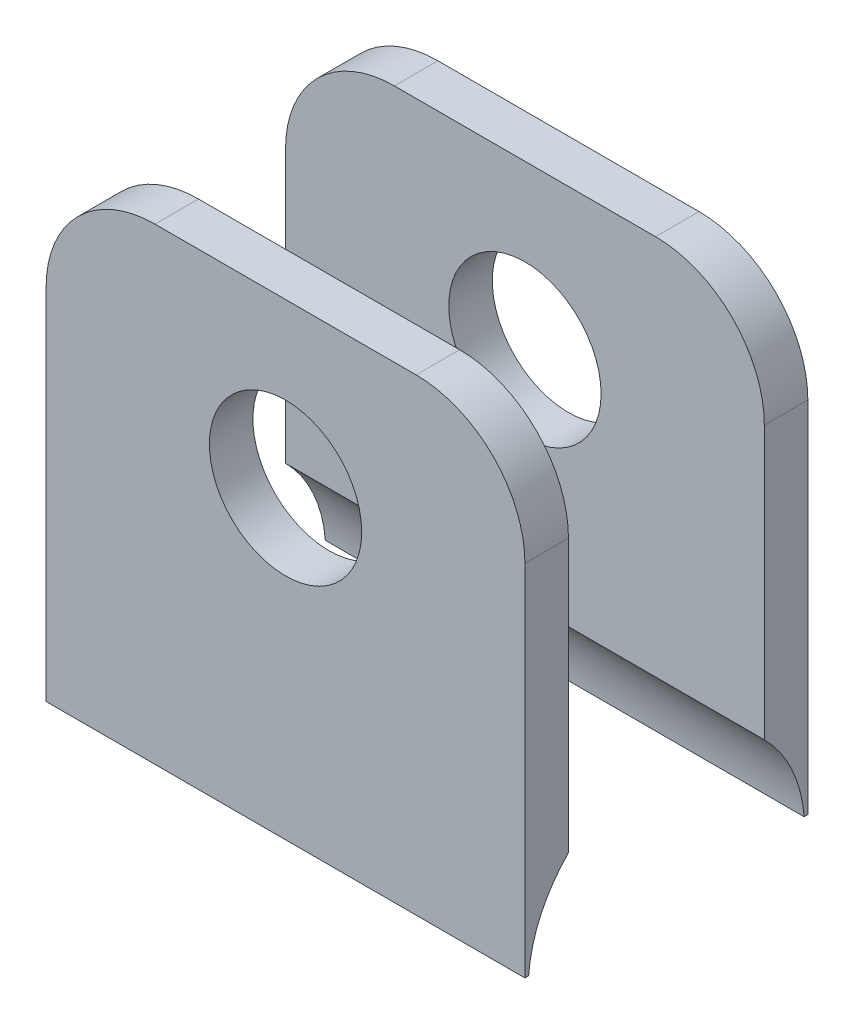
SolidWorks part; units mm, degrees
ref_plane "Front Plane" through (0, 0, 0) normal (0, 0, 1) x (1, 0, 0)
ref_plane "Top Plane" through (0, 0, 0) normal (0, 1, 0) x (1, 0, 0)
ref_plane "Right Plane" through (0, 0, 0) normal (1, 0, 0) x (0, 0, -1)
sketch3d "3DSketch1" plane through (0, 0, 0) normal (0, 0, 1) x (1, 0, 0)
  dimension "D1" = 9
sketch "Sketch2" plane through (0, 0, 9) normal (0, 0, 1) x (1, 0, 0)
  line L0 (-22, 0) -> (22, 0) construction
  line L1 (0, 0) -> (0, 15) construction
  line L2 (-22, 0) -> (-22, 15)
  line L3 (-22, 15) -> (22, 15)
  line L4 (22, 15) -> (22, -28)
  line L5 (22, -28) -> (-22, -28)
  line L6 (-22, -28) -> (-22, 0)
  circle A0 centre (0, 0) radius 7
  point P4 (0, 0)
  dimension "D1" = 14
  dimension "D2" = 15
  dimension "D3" = 28
  dimension "D4" = 44
extrude "Boss-Extrude1" add sketch "Sketch2" along normal blind 4
fillet "Fillet1" radius 10 2 edges at (22, 15, 11) (-22, 15, 11)
mirror "Mirror2" about plane through (0, 0, 0) normal (0, 0, 1) of bodies 101
sketch "Sketch3" plane through (0, 0, 0) normal (1, 0, 0) x (0, 0, -1)
  line L0 (-13, -28) -> (13, -28) construction
  line L1 (0, 0) -> (0, -29) construction
  circle A0 centre (0, -29) radius 12.7
  dimension "D1" = 25.4
  dimension "D2" = 29
extrude "Cut-Extrude1" cut sketch "Sketch3" against normal blind 25 and the other way blind 25
